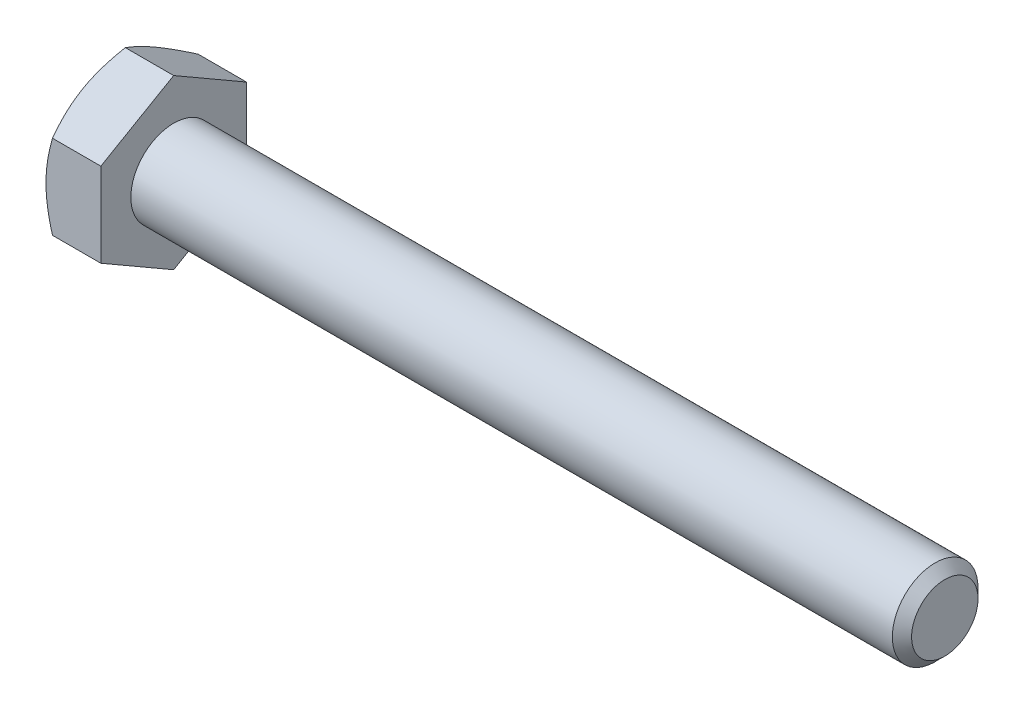
SolidWorks part; units mm, degrees
ref_plane "Front Plane" through (0, 0, 0) normal (0, 0, 1) x (1, 0, 0)
ref_plane "Top Plane" through (0, 0, 0) normal (0, 1, 0) x (1, 0, 0)
ref_plane "Right Plane" through (0, 0, 0) normal (1, 0, 0) x (0, 0, -1)
sketch "Sketch1" plane through (0, 0, 0) normal (0, 0, 1) x (1, 0, 0)
  line L0 (-48.2, 0) -> (48.2, 0) construction
  line L1 (-41.8, 8.5) -> (-41.8, -8.5) construction
  line L2 (-48.2, 8.5) -> (-48.2, -8.5) construction
  line L3 (48.2, 5) -> (48.2, -5) construction
  point P8 (42.95, -5)
  dimension "Thread Dia" = 10
  dimension "Hex" = 17
  dimension "Head Ht" = 6.4
  dimension "Length" = 90
  dimension "D1" = 5.25
ref_plane "Plane2" through (48.2, 0, 0) normal (1, 0, 0) x (0, 0, -1)
sketch "Sketch2" plane through (48.2, 0, 0) normal (1, 0, 0) x (0, 0, -1)
  circle A0 centre (0, 0) radius 5
extrude "Boss-Extrude1" add sketch "Sketch2" against normal up to vertex (90 mm away) up to point (-41.8, -8.5, 0)
sketch "Sketch4" plane through (48.2, 0, 0) normal (1, 0, 0) x (0, 0, -1)
  circle A1 centre (0, 0) radius 5
  circle A2 centre (0, 0) radius 5
  dimension "D1" = 0
curve "Helix/Spiral1" [suppressed] pitch 1.5 height 91.5 turns 61 parameters "Pitch"=1.5
chamfer "Chamfer1" distance 1.125 angle 45 1 edges at (48.2, 0, -5)
sketch "Sketch5" plane through (0, 0, 0) normal (0, 0, 1) x (1, 0, 0)
  line L0 (48.2, 5) -> (48.7625, 4.0257)
  line L1 (48.7625, 4.0257) -> (48.95, 4.0257)
  line L2 (48.95, 4.0257) -> (49.5125, 5)
  line L3 (48.2, 5) -> (49.5125, 5)
  line L4 (48.8562, 4.0257) -> (48.8562, 5) construction
  line L5 (48.4812, 4.5129) -> (49.2312, 4.5129) construction
  line L6 (48.2, -5) -> (48.2, 5) construction
  dimension "D1" = 60
  dimension "D2" = 0.1875
  dimension "D3" = 0.75
sweep "Cut-Sweep1" [suppressed] cut profiles "Sketch5" path "Helix/Spiral1"
sketch "Sketch3" plane through (-41.8, 0, 0) normal (-1, 0, 0) x (0, 0, 1)
  line L0 (0, 8.5) -> (0, -8.5) construction
  line L1 (-8.5, -4.9075) -> (0, -9.815)
  line L2 (0, -9.815) -> (8.5, -4.9075)
  line L3 (8.5, -4.9075) -> (8.5, 4.9075)
  line L4 (8.5, 4.9075) -> (0, 9.815)
  line L5 (0, 9.815) -> (-8.5, 4.9075)
  line L6 (-8.5, 4.9075) -> (-8.5, -4.9075)
  circle A0 centre (0, 0) radius 8.5 construction
extrude "Boss-Extrude2" add sketch "Sketch3" along normal up to vertex (6.4 mm away) up to point (-48.2, -8.5, 0)
sketch "Sketch6" plane through (-48.2, 0, 0) normal (-1, 0, 0) x (0, 0, 1)
  circle A0 centre (0, 0) radius 8.5 construction
  circle A1 centre (0, 0) radius 8.5
extrude "Cut-Extrude1" cut sketch "Sketch6" against normal through all draft 60 flip side to cut
sketch "Sketch7" plane through (-48.2, 0, 0) normal (-1, 0, 0) x (0, 0, 1)
  line L0 (0, 0) -> (0, 8.5) construction
  line L2 (0, 8.5) -> (0, -8.5) construction
  line L3 (-7.3612, 4.25) -> (7.3612, 4.25) construction
  circle A1 centre (0, 0) radius 8.5 construction
  text T0 "10.9" font "Arial" height in points 12
  point P8 (0, 4.25)
extrude "Cut-Extrude2" cut sketch "Sketch7" against normal blind 0.25
sketch "Sketch9" plane through (0, 0, 0) normal (0, 0, 1) x (1, 0, 0)
  line L0 (-41.8, 5) -> (-41.8, 0)
  line L1 (-41.8, 0) -> (31.2, 0)
  line L2 (31.2, 0) -> (26.2, 5)
  line L3 (26.2, 5) -> (-41.8, 5)
  line L4 (-48.2, 0) -> (48.2, 0) construction
  line L5 (-41.8, 8.5) -> (-41.8, -8.5) construction
  line L6 (48.2, 5) -> (48.2, -5) construction
  dimension "D1" = 45
  dimension "MinThreadLg" = 22
revolve "Revolve1" [suppressed] add sketch "Sketch9" angle 360 about L1
equation "\"D2@Sketch5\" = \"Pitch@Helix/Spiral1\"*.125"
equation "\"D3@Sketch5\" = \"Pitch@Helix/Spiral1\"*.50"
equation "\"D3@Helix/Spiral1\" = \"Length@Sketch1\"+\"Pitch@Helix/Spiral1\""
equation "\"D1@Chamfer1\" = \"Pitch@Helix/Spiral1\"*.750"
equation "\"D1@Sketch1\" = \"Pitch@Helix/Spiral1\"*3.50"
